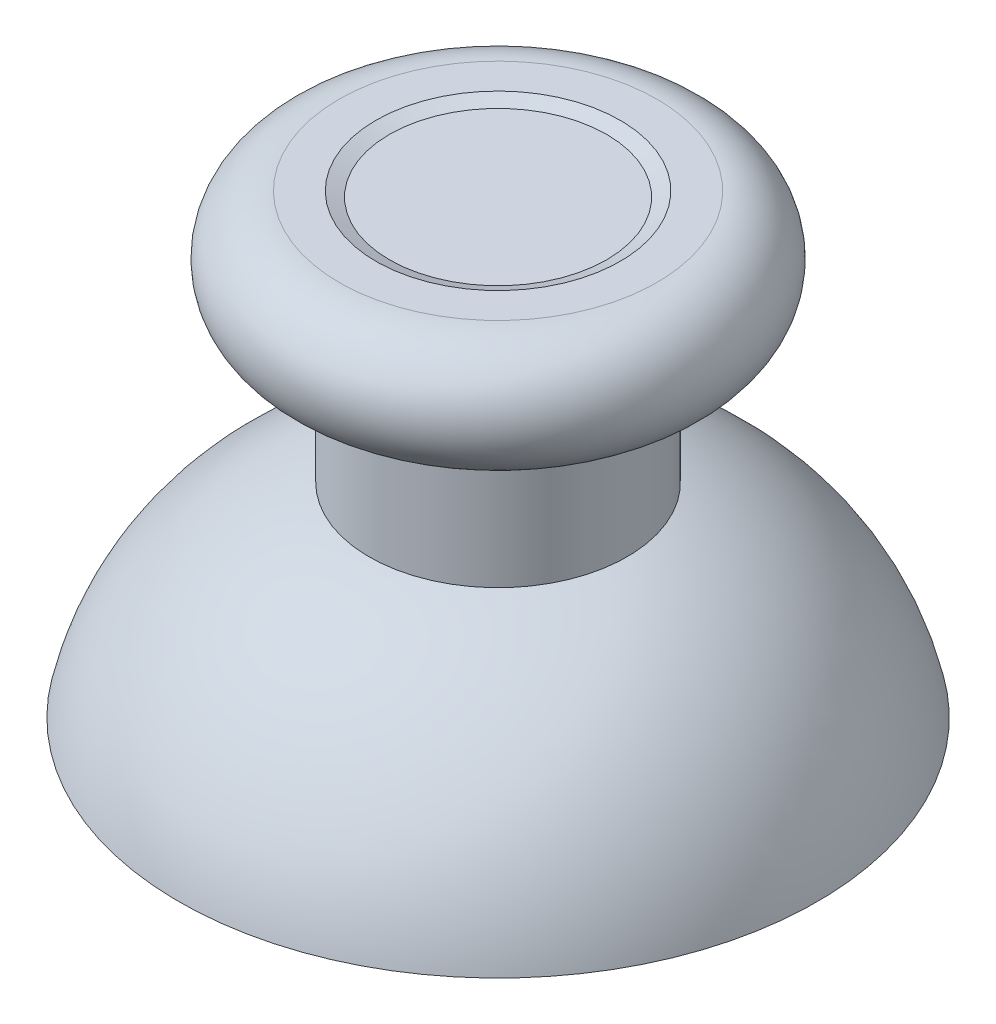
SolidWorks part; units mm, degrees
material "Rubber"
ref_plane "Front" through (0, 0, 0) normal (0, 0, 1) x (1, 0, 0)
ref_plane "Top" through (0, 0, 0) normal (0, 1, 0) x (1, 0, 0)
ref_plane "Right" through (0, 0, 0) normal (1, 0, 0) x (0, 0, -1)
sketch "Sketch1" plane through (0, 0, 0) normal (0, 0, 1) x (1, 0, 0)
  line L0 (0, 0) -> (11.75, 0)
  line L1 (0, 0) -> (0, -20.3128) construction
  line L2 (4.75, 7.5) -> (4.75, 12.5)
  line L3 (4.75, 12.5) -> (5.85, 12.5)
  line L4 (0, 0) -> (0, 16.8)
  line L5 (0, 16.8) -> (5.85, 16.8)
  line L6 (4.5, 16.8) -> (4, 16.6)
  line L7 (4, 16.6) -> (0, 16.6)
  line L8 (0, 6.5) -> (2, 6.5)
  arc A0 (4.75, 7.5) -> (11.75, 0) centre (1.9745, -2.1071) cw
  arc A1 (5.85, 12.5) -> (5.85, 16.8) centre (5.85, 14.65) ccw
  arc A2 (10.1492, 0) -> (2, 6.5) centre (2, -1.8584) ccw
  dimension "D5" = 16
  dimension "D7" = 10
  dimension "D11" = 0.25
  dimension "D1" = 23.5
  dimension "D2" = 9.5
  dimension "D3" = 5
  dimension "D4" = 4.3
  dimension "D6" = 7.5
  dimension "D8" = 0.2
  dimension "D9" = 4
  dimension "D10" = 4.5
  dimension "D12" = 6.5
  dimension "D13" = 2
revolve "Revolve1" add sketch "Sketch1" angle 360 about L1 region at (4.1618, 10.5801, 0)
sketch "Sketch2" plane through (0, 6.5, 0) normal (0, -1, 0) x (1, 0, 0)
  line L0 (0, 0.5) -> (0, -0.5) construction
  line L1 (1.5, 0.5) -> (1.5, -0.5)
  line L2 (-1.5, 0.5) -> (-1.5, -0.5)
  circle A0 centre (0, 0) radius 2.5
  arc A1 (1.5, 0.5) -> (-1.5, 0.5) centre (0, 0.5) ccw
  arc A2 (-1.5, -0.5) -> (1.5, -0.5) centre (0, -0.5) ccw
  circle A3 centre (0, 0) radius 0.5
  point P5 (0, 0)
  circle M1 centre (0, 0) radius 2
  dimension "D1" = 5
  dimension "D3" = 4
  dimension "D4" = 1
  dimension "D2" = 3
extrude "Boss-Extrude2" add sketch "Sketch2" along normal blind 4 contours A0 M1 | L2 A2 L1 A1 A3 | L0 A3 | A2 L2 A1 M1 | A3 L0 | A2 A1 L1 M1 region at (0.2122, 6.5, 0) region at (-0.2122, 6.5, 0) region at (1.5681, 6.5, 0) region at (1.45, 6.5, 0) region at (-1.5681, 6.5, 0) region at (-2.4293, 6.5, 0)
extrude "Cut-Extrude1" cut sketch "Sketch2<3>" along normal through all contours L2 A2 L1 A1 A3 | A3 region at (1.45, 6.5, 0)
sketch "Sketch2<3>" plane through (0, 6.5, 0) normal (0, -1, 0) x (1, 0, 0) same geometry as "Sketch2"
